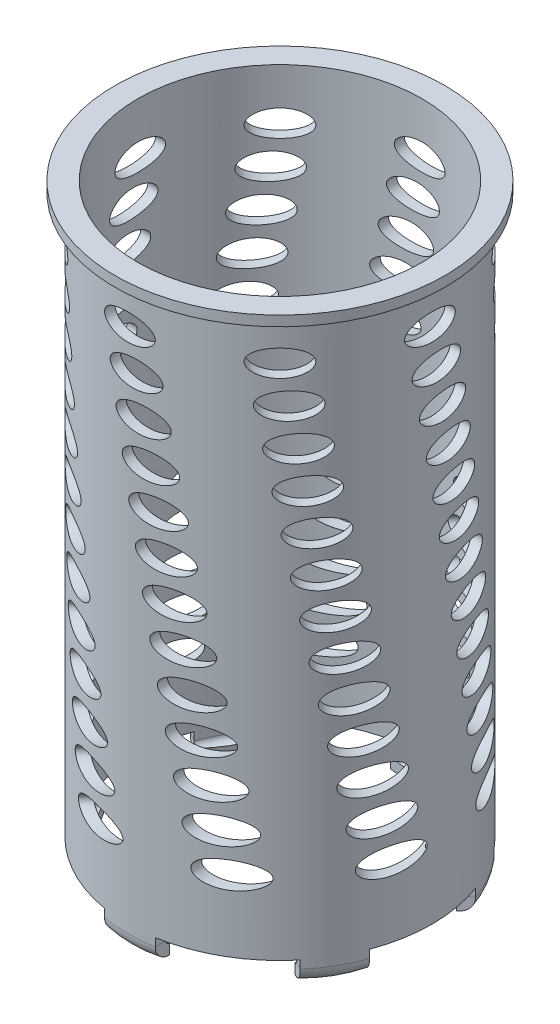
SolidWorks part; units mm, degrees
ref_plane "Front Plane" through (0, 0, 0) normal (0, 0, 1) x (1, 0, 0)
ref_plane "Top Plane" through (0, 0, 0) normal (0, 1, 0) x (1, 0, 0)
ref_plane "Right Plane" through (0, 0, 0) normal (1, 0, 0) x (0, 0, -1)
sketch "Sketch2" plane through (0, 0, 0) normal (1, 0, 0) x (0, 0, -1)
  line L0 (0, 0) -> (0, 69.85) construction
  line L1 (-19.05, 0) -> (-19.05, 69.85)
  line L2 (-19.05, 69.85) -> (-20.6375, 69.85)
  dimension "D1" = 38.1
  dimension "D2" = 41.275
  dimension "D3" = 69.85
revolve "Revolve-Thin1" add sketch "Sketch2" angle 360 about L0
ref_plane "Plane1" through (0, 0, 27.94) normal (0, 0, 1) x (1, 0, 0)
sketch "Sketch3" plane through (0, 0, 27.94) normal (0, 0, 1) x (1, 0, 0)
  line L0 (0, 64.77) -> (9.0519, 64.77) construction
  line L2 (20.6375, 71.12) -> (-20.6375, 71.12) construction
  ellipse E0 centre (0, 64.77) end of major axis (3.175, 64.77) minor radius 1.651
  ellipse E1 centre (0.8211, 60.1133) end of major axis (3.9961, 60.1133) minor radius 1.651
  ellipse E2 centre (1.6422, 55.4567) end of major axis (-1.5328, 55.4567) minor radius 1.651
  ellipse E3 centre (2.4633, 50.8) end of major axis (5.6383, 50.8) minor radius 1.651
  ellipse E4 centre (3.2844, 46.1433) end of major axis (6.4594, 46.1433) minor radius 1.651
  ellipse E5 centre (4.1055, 41.4867) end of major axis (7.2805, 41.4867) minor radius 1.651
  ellipse E6 centre (4.9266, 36.83) end of major axis (8.1016, 36.83) minor radius 1.651
  ellipse E7 centre (5.7477, 32.1733) end of major axis (8.9227, 32.1733) minor radius 1.651
  ellipse E8 centre (6.5688, 27.5167) end of major axis (3.3938, 27.5167) minor radius 1.651
  ellipse E9 centre (7.3899, 22.86) end of major axis (10.5649, 22.86) minor radius 1.651
  ellipse E10 centre (8.211, 18.2033) end of major axis (11.386, 18.2033) minor radius 1.651
  ellipse E11 centre (9.0321, 13.5467) end of major axis (5.8571, 13.5467) minor radius 1.651
  ellipse E12 centre (9.8532, 8.89) end of major axis (6.6782, 8.89) minor radius 1.651
  dimension "D1" = 6.35
  dimension "D2" = 13
  dimension "D3" = 55.88
  dimension "D4" = 3.302
  dimension "D5" = 6.35
extrude "Cut-Extrude1" cut sketch "Sketch3" against normal up to next
pattern_circular "CirPattern1" count 8 over 360 about axis through (0, 71.12, 0) along (0, -1, 0) of "Cut-Extrude1"
sketch "Sketch9" plane through (0, 0, 0) normal (0, -1, 0) x (1, 0, 0)
  line L0 (0, 0) -> (0, 18.1389) construction
  line L2 (-3.175, 17.4942) -> (-3.175, 18.7836)
  line L4 (3.175, 17.4942) -> (3.175, 18.7836)
  line L5 (-3.175, 18.1389) -> (3.175, 18.1389) construction
  line L6 (13.5629, 11.4967) -> (14.6795, 12.1414)
  line L7 (16.7379, 5.9975) -> (17.8545, 6.6421)
  line L8 (16.7379, -5.9975) -> (17.8545, -6.6421)
  line L9 (13.5629, -11.4967) -> (14.6795, -12.1414)
  line L10 (3.175, -17.4942) -> (3.175, -18.7836)
  line L11 (-3.175, -17.4942) -> (-3.175, -18.7836)
  line L12 (-13.5629, -11.4967) -> (-14.6795, -12.1414)
  line L13 (-16.7379, -5.9975) -> (-17.8545, -6.6421)
  line L14 (-16.7379, 5.9975) -> (-17.8545, 6.6421)
  line L15 (-13.5629, 11.4967) -> (-14.6795, 12.1414)
  arc A0 (-3.175, 18.7836) -> (-14.6795, 12.1414) centre (0, 0) ccw
  arc A1 (-3.175, 17.4942) -> (-13.5629, 11.4967) centre (0, 0) ccw
  circle A2 centre (0, 0) radius 19.05 construction
  circle A3 centre (0, 0) radius 17.78 construction
  arc A4 (0, 17.78) -> (-3.175, 17.4942) centre (0, 0) ccw construction
  arc A5 (3.175, 17.4942) -> (0, 17.78) centre (0, 0) ccw construction
  arc A6 (3.175, 18.7836) -> (-3.175, 18.7836) centre (0, 0) ccw construction
  arc A7 (17.8545, 6.6421) -> (14.6795, 12.1414) centre (0, 0) ccw construction
  arc A8 (16.7379, 5.9975) -> (15.3979, 8.89) centre (0, 0) ccw construction
  arc A9 (15.3979, 8.89) -> (13.5629, 11.4967) centre (0, 0) ccw construction
  arc A10 (14.6795, -12.1414) -> (17.8545, -6.6421) centre (0, 0) ccw construction
  arc A11 (13.5629, -11.4967) -> (15.3979, -8.89) centre (0, 0) ccw construction
  arc A12 (15.3979, -8.89) -> (16.7379, -5.9975) centre (0, 0) ccw construction
  arc A13 (-3.175, -18.7836) -> (3.175, -18.7836) centre (0, 0) ccw construction
  arc A14 (-3.175, -17.4942) -> (0, -17.78) centre (0, 0) ccw construction
  arc A15 (0, -17.78) -> (3.175, -17.4942) centre (0, 0) ccw construction
  arc A16 (-17.8545, -6.6421) -> (-14.6795, -12.1414) centre (0, 0) ccw construction
  arc A17 (-16.7379, -5.9975) -> (-15.3979, -8.89) centre (0, 0) ccw construction
  arc A18 (-15.3979, -8.89) -> (-13.5629, -11.4967) centre (0, 0) ccw construction
  arc A19 (-14.6795, 12.1414) -> (-17.8545, 6.6421) centre (0, 0) ccw construction
  arc A20 (-13.5629, 11.4967) -> (-15.3979, 8.89) centre (0, 0) ccw construction
  arc A21 (-15.3979, 8.89) -> (-16.7379, 5.9975) centre (0, 0) ccw construction
  arc A22 (-17.8545, 6.6421) -> (-17.8545, -6.6421) centre (0, 0) ccw
  arc A23 (-14.6795, 12.1414) -> (-17.8545, 6.6421) centre (0, 0) ccw construction
  arc A24 (-16.7379, 5.9975) -> (-16.7379, -5.9975) centre (0, 0) ccw
  arc A25 (-13.5629, 11.4967) -> (-15.3979, 8.89) centre (0, 0) ccw construction
  arc A26 (-15.3979, 8.89) -> (-16.7379, 5.9975) centre (0, 0) ccw construction
  arc A27 (-13.5629, -11.4967) -> (-3.175, -17.4942) centre (0, 0) ccw
  arc A28 (-16.7379, -5.9975) -> (-15.3979, -8.89) centre (0, 0) ccw construction
  arc A29 (-15.3979, -8.89) -> (-13.5629, -11.4967) centre (0, 0) ccw construction
  arc A30 (-14.6795, -12.1414) -> (-3.175, -18.7836) centre (0, 0) ccw
  arc A31 (-17.8545, -6.6421) -> (-14.6795, -12.1414) centre (0, 0) ccw construction
  arc A32 (3.175, -17.4942) -> (13.5629, -11.4967) centre (0, 0) ccw
  arc A33 (-3.175, -17.4942) -> (0, -17.78) centre (0, 0) ccw construction
  arc A34 (0, -17.78) -> (3.175, -17.4942) centre (0, 0) ccw construction
  arc A35 (3.175, -18.7836) -> (14.6795, -12.1414) centre (0, 0) ccw
  arc A36 (-3.175, -18.7836) -> (3.175, -18.7836) centre (0, 0) ccw construction
  arc A37 (16.7379, -5.9975) -> (16.7379, 5.9975) centre (0, 0) ccw
  arc A38 (13.5629, -11.4967) -> (15.3979, -8.89) centre (0, 0) ccw construction
  arc A39 (15.3979, -8.89) -> (16.7379, -5.9975) centre (0, 0) ccw construction
  arc A40 (17.8545, -6.6421) -> (17.8545, 6.6421) centre (0, 0) ccw
  arc A41 (14.6795, -12.1414) -> (17.8545, -6.6421) centre (0, 0) ccw construction
  arc A42 (13.5629, 11.4967) -> (3.175, 17.4942) centre (0, 0) ccw
  arc A43 (16.7379, 5.9975) -> (15.3979, 8.89) centre (0, 0) ccw construction
  arc A44 (15.3979, 8.89) -> (13.5629, 11.4967) centre (0, 0) ccw construction
  arc A45 (14.6795, 12.1414) -> (3.175, 18.7836) centre (0, 0) ccw
  arc A46 (17.8545, 6.6421) -> (14.6795, 12.1414) centre (0, 0) ccw construction
  point P9 (0, 18.1389)
  point P42 (0, 0)
  dimension "D1" = 6.35
  dimension "D2" = 6
sketch "Sketch12" plane through (0, 0, 0) normal (1, 0, 0) x (0, 0, -1)
  line L0 (-17.78, -1.016) -> (-17.78, 0)
  arc A0 (-17.78, -1.016) -> (-17.018, -1.778) centre (-17.018, -1.016) ccw
  dimension "D1" = 1.778
  dimension "D2" = 1.016
ref_plane "Plane6" through (0, 0, 17.78) normal (0, 1, 0) x (1, 0, 0)
sketch "Sketch13" plane through (0, 0, 17.78) normal (0, 1, 0) x (1, 0, 0)
  line L6 (3.175, 0.2858) -> (3.175, -1.0036)
  line L13 (-3.175, 0.2858) -> (-3.175, -1.0036)
  arc A3 (3.175, 0.2858) -> (-3.175, 0.2858) centre (0, 17.78) cw
  circle A4 centre (0, 17.78) radius 17.78 construction
  circle A8 centre (0, 17.78) radius 19.05 construction
  arc A9 (3.175, -1.0036) -> (-3.175, -1.0036) centre (0, 17.78) cw
  point P14 (0, 0)
  dimension "D1" = 6.35
sweep "Sweep1" add profiles "Sketch13" path "Sketch12"
pattern_circular "CirPattern2" count 6 over 360 about axis through (0, 0, 0) along (0, 1, 0) of "Sweep1"
